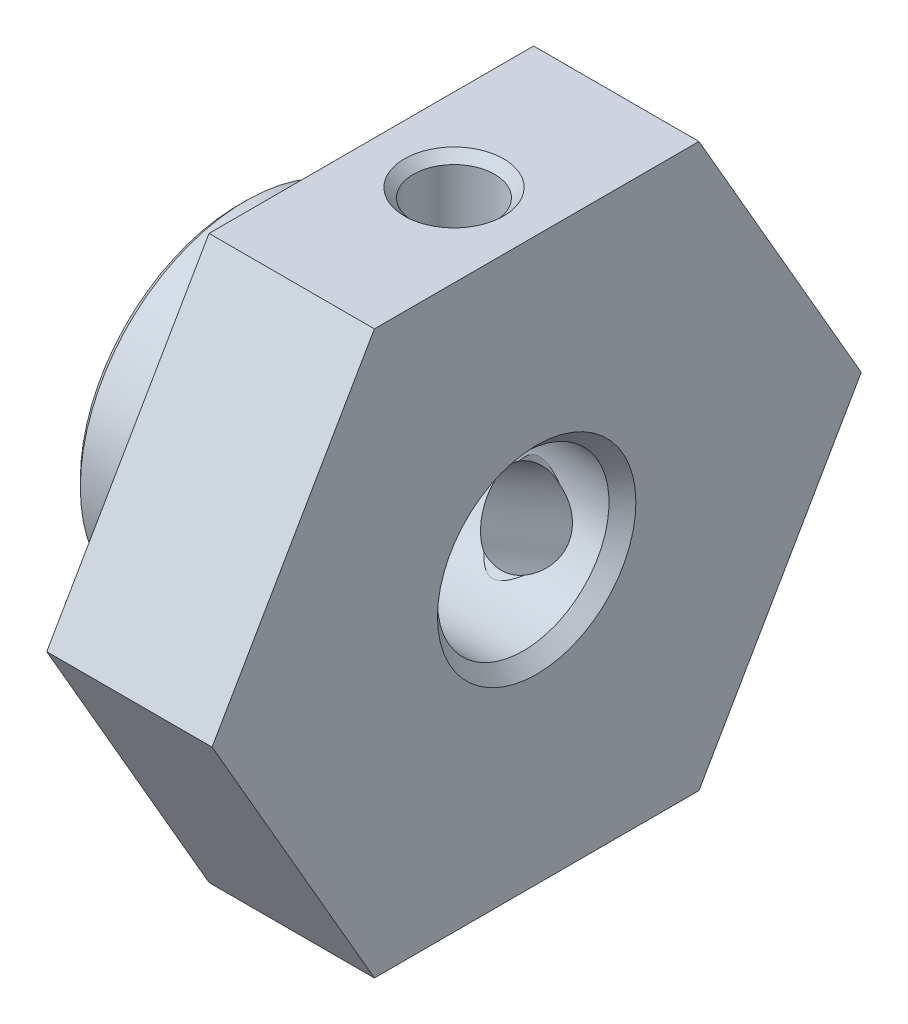
SolidWorks part; units mm, degrees
ref_plane "Front Plane" through (0, 0, 0) normal (0, 0, 1) x (1, 0, 0)
ref_plane "Top Plane" through (0, 0, 0) normal (0, 1, 0) x (1, 0, 0)
ref_plane "Right Plane" through (0, 0, 0) normal (1, 0, 0) x (0, 0, -1)
ref_plane "Plane1" through (0, 0, 0) normal (0, 0, 1) x (1, 0, 0)
sketch "Sketch1" plane through (0, 0, 0) normal (0, 0, 1) x (1, 0, 0)
  line L0 (0, 0) -> (0, 4.8)
  line L1 (0, 4.8) -> (0.2, 5)
  line L2 (0.2, 5) -> (4, 5)
  line L3 (4, 5) -> (4, 10.2)
  line L4 (4, 10.2) -> (9, 10.2)
  line L5 (9, 10.2) -> (9, 0)
  line L6 (9, 0) -> (0, 0)
  line L7 (9, 0) -> (0, 0) construction
revolve "Revolve1" add sketch "Sketch1" angle 360 about L7 reverse direction yes
ref_plane "Plane2" through (0, 0, 0) normal (0, 0, 1) x (1, 0, 0)
sketch "Sketch2" plane through (0, 0, 0) normal (0, 0, 1) x (1, 0, 0)
  line L0 (0, 0) -> (0, 3)
  line L1 (0, 3) -> (0.406, 2.594)
  line L2 (0.406, 2.594) -> (8.594, 2.594)
  line L3 (8.594, 2.594) -> (9, 3)
  line L4 (9, 3) -> (9, 0)
  line L5 (9, 0) -> (0, 0)
  line L6 (9, 0) -> (0, 0) construction
revolve "Cut-Revolve1" cut sketch "Sketch2" angle 360 about L6 reverse direction yes
ref_plane "Plane3" through (0, 0, 0) normal (1, 0, 0) x (0, 0, -1)
sketch "Sketch3" plane through (0, 0, 0) normal (1, 0, 0) x (0, 0, -1)
  line L0 (-17, -17) -> (17, -17)
  line L1 (17, -17) -> (17, 17)
  line L2 (17, 17) -> (-17, 17)
  line L3 (-17, 17) -> (-17, -17)
  line L4 (-9.815, 0) -> (-4.9075, -8.5)
  line L5 (-4.9075, -8.5) -> (4.9075, -8.5)
  line L6 (4.9075, -8.5) -> (9.815, 0)
  line L7 (9.815, 0) -> (4.9075, 8.5)
  line L8 (4.9075, 8.5) -> (-4.9075, 8.5)
  line L9 (-4.9075, 8.5) -> (-9.815, 0)
extrude "Cut-Extrude1" cut sketch "Sketch3" along normal blind 9
ref_plane "Plane4" through (6.5, 0, 0) normal (1, 0, 0) x (0, 0, -1)
sketch "Sketch4" plane through (6.5, 0, 0) normal (1, 0, 0) x (0, 0, -1)
  line L0 (0, 8.5) -> (1.5, 8.5)
  line L1 (1.5, 8.5) -> (1.2295, 8.2295)
  line L2 (1.2295, 8.2295) -> (1.2295, 2.3645)
  line L3 (1.2295, 2.3645) -> (1.5, 2.094)
  line L4 (1.5, 2.094) -> (0, 2.094)
  line L5 (0, 2.094) -> (0, 8.5)
  line L6 (0, 2.094) -> (0, 8.5) construction
revolve "Cut-Revolve2" cut sketch "Sketch4" angle 360 about L6 reverse direction yes
ref_plane "Plane5" through (6.5, 0, 0) normal (1, 0, 0) x (0, 0, -1)
sketch "Sketch5" plane through (6.5, 0, 0) normal (1, 0, 0) x (0, 0, -1)
  line L0 (7.3612, -4.25) -> (6.6112, -5.549)
  line L1 (6.6112, -5.549) -> (6.5122, -5.1795)
  line L2 (6.5122, -5.1795) -> (1.433, -2.247)
  line L3 (1.433, -2.247) -> (1.0635, -2.346)
  line L4 (1.0635, -2.346) -> (1.8135, -1.047)
  line L5 (1.8135, -1.047) -> (7.3612, -4.25)
  line L6 (1.8135, -1.047) -> (7.3612, -4.25) construction
revolve "Cut-Revolve3" cut sketch "Sketch5" angle 360 about L6 reverse direction yes
